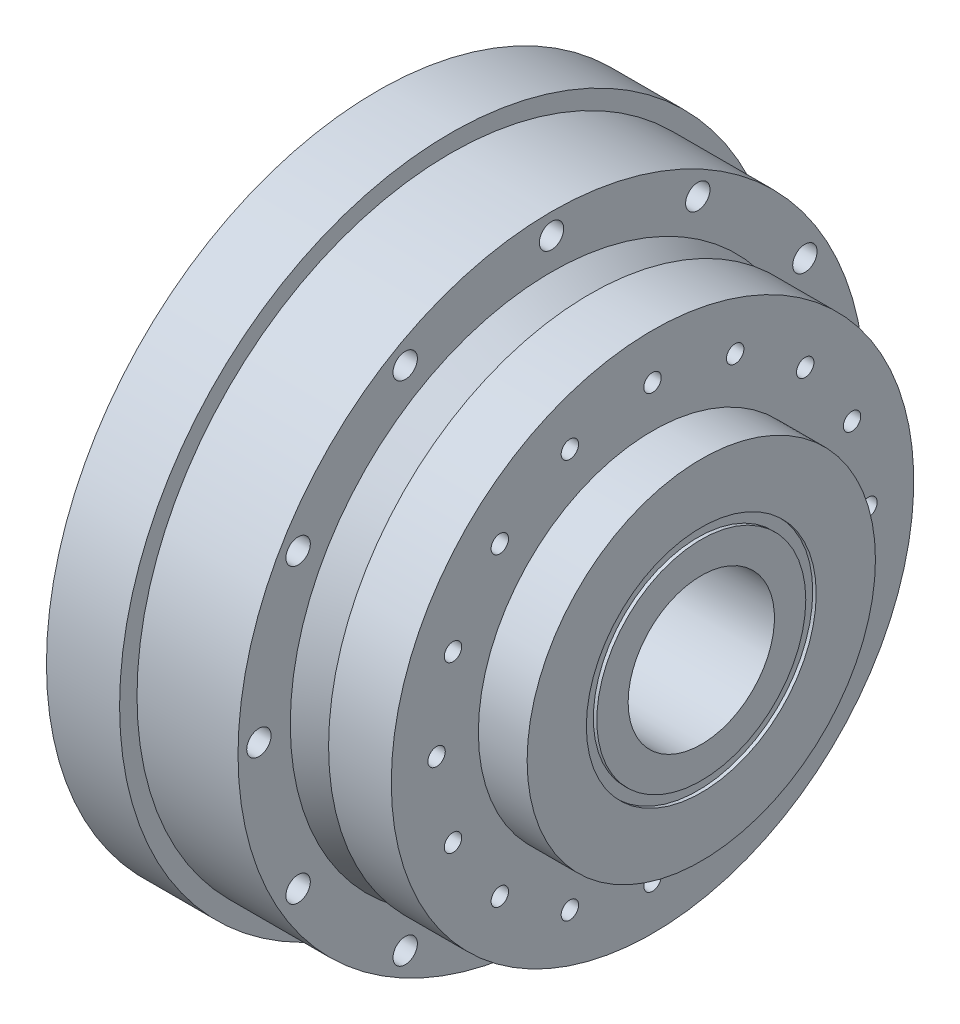
SolidWorks part; units mm, degrees
ref_plane "前视基准面" through (0, 0, 0) normal (0, 0, 1) x (1, 0, 0)
ref_plane "上视基准面" through (0, 0, 0) normal (0, 1, 0) x (1, 0, 0)
ref_plane "右视基准面" through (0, 0, 0) normal (1, 0, 0) x (0, 0, -1)
sketch "草图1" plane through (0, 0, 0) normal (0, 0, 1) x (1, 0, 0)
  line L0 (-65.2008, 0) -> (80.5899, 0) construction
  line L1 (0, 10.5) -> (0, 15)
  line L2 (0, 15) -> (5, 15)
  line L3 (5, 15) -> (5, 47.5)
  line L4 (5, 47.5) -> (15.5, 47.5)
  line L5 (15.5, 47.5) -> (15.5, 45)
  line L6 (15.5, 45) -> (30, 45)
  line L7 (30, 45) -> (30, 37.5)
  line L9 (35.5, 34.3246) -> (35.5, 37.5)
  line L10 (35.5, 37.5) -> (44.5, 37.5)
  line L11 (44.5, 37.5) -> (44.5, 25)
  line L12 (44.5, 25) -> (51.5, 25)
  line L13 (51.5, 25) -> (51.5, 10.5)
  line L14 (0, 10.5) -> (51.5, 10.5)
  line L15 (0, 0) -> (0, 43.251) construction
  line L17 (30, 37.5) -> (35.5, 34.3246)
  dimension "D1" = 95
  dimension "D2" = 30
  dimension "D3" = 21
  dimension "D4" = 90
  dimension "D5" = 75
  dimension "D6" = 50
  dimension "D7" = 5
  dimension "D8" = 10.5
  dimension "D9" = 25
  dimension "D10" = 51.5
  dimension "D11" = 9
  dimension "D12" = 7
  dimension "D13" = 60
revolve "旋转1" add sketch "草图1" angle 360 about L0
ref_axis "基准轴1" through (51.5, 0, 0) along (-1, 0, 0)
sketch "草图5" plane through (5, 0, 0) normal (-1, 0, 0) x (0, 0, 1)
  line L0 (0, 0) -> (0, 40.0957) construction
  circle A0 centre (0, 0) radius 42 construction
  circle A1 centre (0, 42) radius 1.75
  dimension "D1" = 84
  dimension "D2" = 3.5
extrude "切除-拉伸1" cut sketch "草图5" against normal up to next
pattern_circular "阵列(圆周)2" count 12 over 360 about axis through (51.5, 0, 0) along (-1, 0, 0) of "切除-拉伸1"
hole_wizard "M3 螺纹孔4" positions "草图16" profile "草图15" tap size "M3" standard "GB"
sketch "草图16" plane through (44.5, 0, 0) normal (1, 0, 0) x (0, 0, -1)
  line L0 (0, 0) -> (0, 44.049) construction
  circle A0 centre (0, 0) radius 31 construction
  point P0 (0, 31)
  dimension "D1" = 62
sketch "草图15" plane through (44.5, 31, 0) normal (0, 1, 0) x (0, 0, -1)
  line L0 (0, 0) -> (0, 14.2511)
  line L1 (0, 14.2511) -> (1.25, 13.5)
  line L2 (1.25, 13.5) -> (1.25, 0)
  line L5 (1.25, 0) -> (0, 0)
  line L10 (0, 14.2511) -> (-1.25, 13.5) construction
  line L11 (0, -6.35) -> (0, 107.95) construction
  dimension "螺纹孔钻头直径" = 2.5
  dimension "螺纹孔钻头深度" = 13.5
  dimension "导头角度" = 118
cosmetic thread "孔螺蚊线5" parameters "D1"=6, "D2"=3
pattern_circular "阵列(圆周)5" count 16 over 360 about axis through (51.5, 0, 0) along (-1, 0, 0) of "M3 螺纹孔4"
hole_wizard "M3 螺纹孔5" positions "草图18" profile "草图17" tap size "M3" standard "GB"
sketch "草图18" plane through (0, 0, 0) normal (-1, 0, 0) x (0, 0, 1)
  line L0 (0, 0) -> (0, 49.351) construction
  circle A0 centre (0, 0) radius 12.75 construction
  point P0 (0, 12.75)
  dimension "D1" = 25.5
sketch "草图17" plane through (0, 12.75, 0) normal (0, 1, 0) x (0, 0, 1)
  line L0 (0, 0) -> (0, 8.2511)
  line L1 (0, 8.2511) -> (1.25, 7.5)
  line L2 (1.25, 7.5) -> (1.25, 0)
  line L5 (1.25, 0) -> (0, 0)
  line L10 (0, 8.2511) -> (-1.25, 7.5) construction
  line L11 (0, -6.35) -> (0, 107.95) construction
  dimension "螺纹孔钻头直径" = 2.5
  dimension "螺纹孔钻头深度" = 7.5
  dimension "导头角度" = 118
cosmetic thread "孔螺蚊线6" parameters "D1"=6, "D2"=3
pattern_circular "阵列(圆周)6" count 6 over 360 about axis through (51.5, 0, 0) along (-1, 0, 0) of "M3 螺纹孔5"
sketch "草图19" plane through (5, 0, 0) normal (-1, 0, 0) x (0, 0, 1)
  circle A0 centre (0, 0) radius 15
  circle A1 centre (0, 0) radius 16.5
  dimension "D1" = 30
  dimension "D2" = 33
extrude "切除-拉伸6" cut sketch "草图19" against normal blind 0.5
sketch "草图20" plane through (51.5, 0, 0) normal (1, 0, 0) x (0, 0, -1)
  circle A0 centre (0, 0) radius 15
  circle A1 centre (0, 0) radius 16.5
  dimension "D1" = 30
  dimension "D2" = 33
extrude "切除-拉伸7" cut sketch "草图20" against normal blind 0.5
